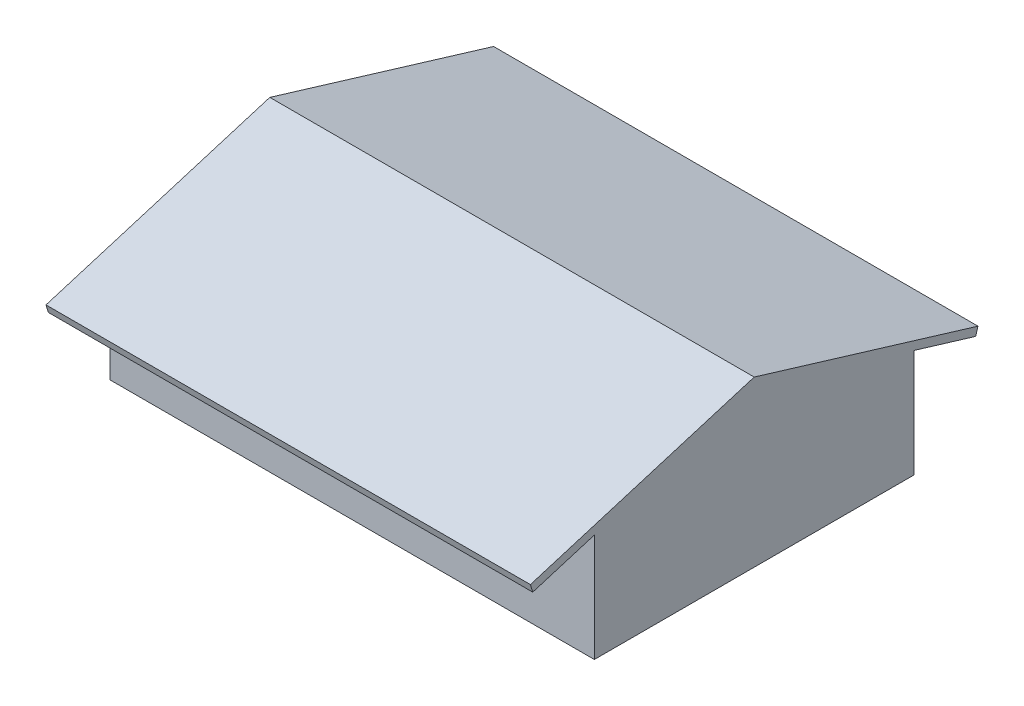
SolidWorks part; units mm, degrees
ref_plane "Front Plane" through (0, 0, 0) normal (0, 0, 1) x (1, 0, 0)
ref_plane "Top Plane" through (0, 0, 0) normal (0, 1, 0) x (1, 0, 0)
ref_plane "Right Plane" through (0, 0, 0) normal (1, 0, 0) x (0, 0, -1)
sketch "Sketch1" plane through (0, 0, 0) normal (1, 0, 0) x (0, 0, -1)
  line L0 (-5029.2, 0) -> (5029.2, 0)
  line L1 (5029.2, 0) -> (5029.2, 3392.194)
  line L2 (5029.2, 3657.6) -> (0, 5181.6)
  line L3 (0, 5181.6) -> (-5029.2, 3657.6)
  line L4 (-5029.2, 3392.194) -> (-5029.2, 0)
  line L5 (-5029.2, 3657.6) -> (-7040.88, 3048)
  line L6 (5029.2, 3657.6) -> (7040.88, 3048)
  line L7 (-5029.2, 3392.194) -> (-6967.2181, 2804.9158)
  line L9 (-7040.88, 3048) -> (-6967.2181, 2804.9158)
  line L10 (5029.2, 3392.194) -> (6967.2181, 2804.9158)
  line L12 (7040.88, 3048) -> (6967.2181, 2804.9158)
  line L14 (4955.5381, 3414.5158) -> (6967.2181, 2804.9158) construction
  line L15 (-4955.5381, 3414.5158) -> (-6967.2181, 2804.9158) construction
  point P0 (-6968.5644, 3048)
  point P4 (0, 0)
  dimension "D1" = 10058.4
  dimension "D2" = 3657.6
  dimension "D3" = 5181.6
  dimension "D4" = 3048
  dimension "D5" = 254
  dimension "D6" = 254
extrude "Boss-Extrude1" add sketch "Sketch1" along normal mid plane 15240
